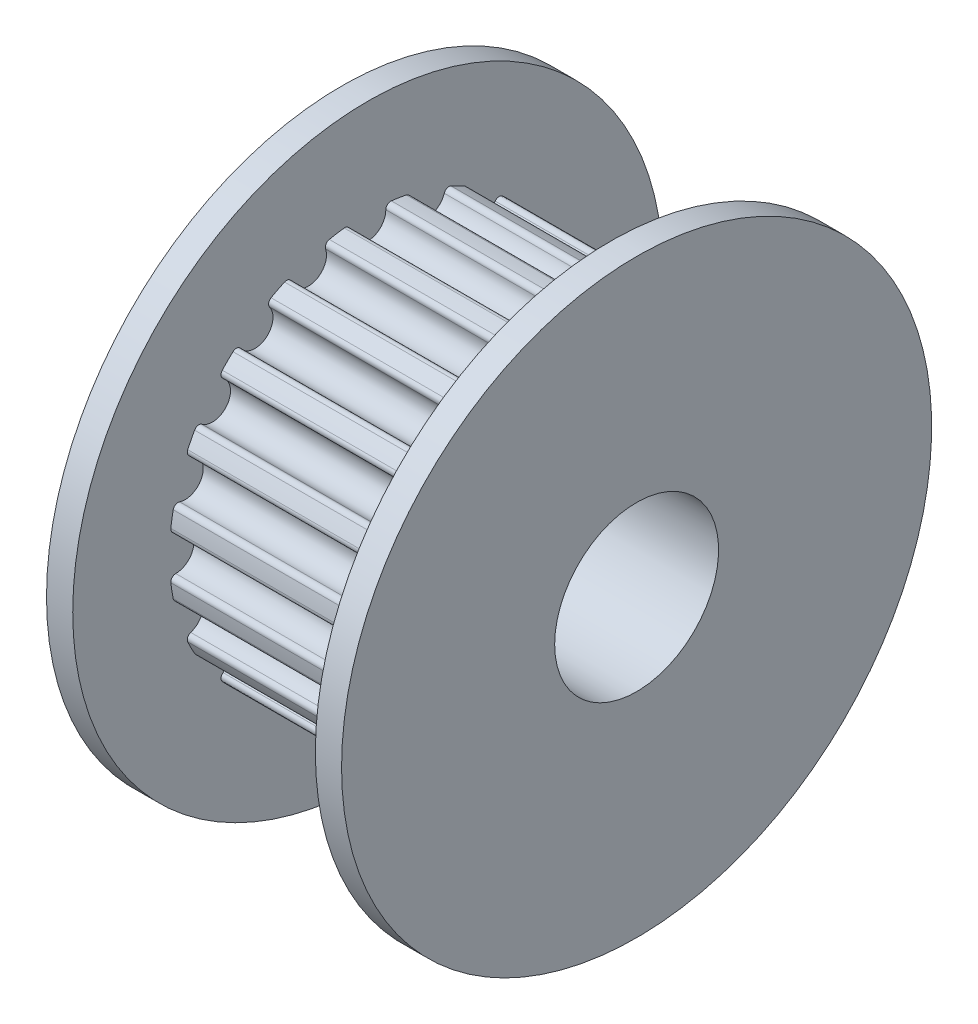
SolidWorks part; units mm, degrees
material "6061-O (SS)"
ref_plane "Сверху" through (0, 0, 0) normal (0, 0, 1) x (1, 0, 0)
ref_plane "Справа" through (0, 0, 0) normal (0, 1, 0) x (1, 0, 0)
ref_plane "Спереди" through (0, 0, 0) normal (1, 0, 0) x (0, 0, -1)
sketch "Эскиз1" plane through (0, 0, 0) normal (0, 0, 1) x (1, 0, 0)
  line L0 (0, 0) -> (0, 9)
  line L2 (0, 9) -> (0.8, 9)
  line L4 (0.8, 6.05) -> (8.2, 6.05)
  line L5 (8.2, 6.05) -> (8.2, 9)
  line L6 (8.2, 9) -> (9, 9)
  line L10 (9, 0) -> (9, 9)
  line L11 (0, 0) -> (9, 0)
  line L12 (0.8, 9) -> (0.8, 6.05)
  dimension "D2" = 0.8
  dimension "D3" = 9
  dimension "D6" = 6.05
  dimension "D8" = 7.4
  dimension "D10" = 9
  dimension "D11" = 9
revolve "Body" add sketch "Эскиз1" angle 360 about L11 region at (4.5, 3.384, 0)
sketch "Эскиз3" plane through (0.8, 0, 0) normal (1, 0, 0) x (0, 0, -1)
  line L0 (0, 0) -> (9.7637, 0) construction
  circle A0 centre (5.5684, -1.8093) radius 0.55
  circle A2 centre (4.7368, -3.4415) radius 0.55
  circle A3 centre (3.4415, -4.7368) radius 0.55
  circle A4 centre (1.8093, -5.5684) radius 0.55
  circle A5 centre (0, -5.855) radius 0.55
  circle A6 centre (5.855, 0) radius 0.55
  circle A7 centre (-1.8093, -5.5684) radius 0.55
  circle A8 centre (-3.4415, -4.7368) radius 0.55
  circle A9 centre (-4.7368, -3.4415) radius 0.55
  circle A10 centre (-5.5684, -1.8093) radius 0.55
  circle A11 centre (-5.855, 0) radius 0.55
  circle A12 centre (-5.5684, 1.8093) radius 0.55
  circle A13 centre (-4.7368, 3.4415) radius 0.55
  circle A14 centre (-3.4415, 4.7368) radius 0.55
  circle A17 centre (-1.8093, 5.5684) radius 0.55
  circle A18 centre (0, 5.855) radius 0.55
  circle A19 centre (1.8093, 5.5684) radius 0.55
  circle A20 centre (3.4415, 4.7368) radius 0.55
  circle A21 centre (4.7368, 3.4415) radius 0.55
  circle A22 centre (5.5684, 1.8093) radius 0.55
  point P45 (0, 0)
  dimension "D1" = 5.855
extrude "20tooth" cut sketch "Эскиз3" along normal up to surface (7.4 mm away) up to face at (8.2, 0, 9)
fillet "Скругление1" radius 0.15 40 edges at (4.5, -0.5223, -6.0274) (4.5, 0.5223, -6.0274) (4.5, -1.3659, -5.8938) (4.5, -2.3593, -5.571) (4.5, -3.1203, -5.1833) (4.5, -3.9654, -4.5693) (4.5, -4.5693, -3.9654) (4.5, -5.1833, -3.1203) (4.5, -5.571, -2.3593) (4.5, -5.8938, -1.3659) (4.5, -6.0274, -0.5223) (4.5, -6.0274, 0.5223) (4.5, -5.8938, 1.3659) (4.5, -5.571, 2.3593) (4.5, -5.1833, 3.1203) (4.5, -4.5693, 3.9654) (4.5, -3.9654, 4.5693) (4.5, -3.1203, 5.1833) (4.5, -2.3593, 5.571) (4.5, -1.3659, 5.8938) (4.5, -0.5223, 6.0274) (4.5, 0.5223, 6.0274) (4.5, 1.3659, 5.8938) (4.5, 2.3593, 5.571) (4.5, 3.1203, 5.1833) (4.5, 3.9654, 4.5693) (4.5, 4.5693, 3.9654) (4.5, 5.1833, 3.1203) (4.5, 5.571, 2.3593) (4.5, 5.8938, 1.3659) (4.5, 6.0274, -0.5223) (4.5, 5.571, -2.3593) (4.5, 4.5693, -3.9654) (4.5, 3.1203, -5.1833) (4.5, 1.3659, -5.8938) (4.5, 2.3593, -5.571) (4.5, 3.9654, -4.5693) (4.5, 6.0274, 0.5223) (4.5, 5.8938, -1.3659) (4.5, 5.1833, -3.1203)
ref_plane "Piano1" through (4.5, 0, 0) normal (1, 0, 0) x (0, 0, -1)
sketch "Schizzo1" plane through (0, 0, 0) normal (-1, 0, 0) x (0, 0, 1)
  circle A0 centre (0, 0) radius 2.5
  dimension "D1" = 5
extrude "Taglio-Estrusione1" cut sketch "Schizzo1" against normal through all
ref_axis "Assi1" through (9, 0, 0) along (-1, 0, 0)
